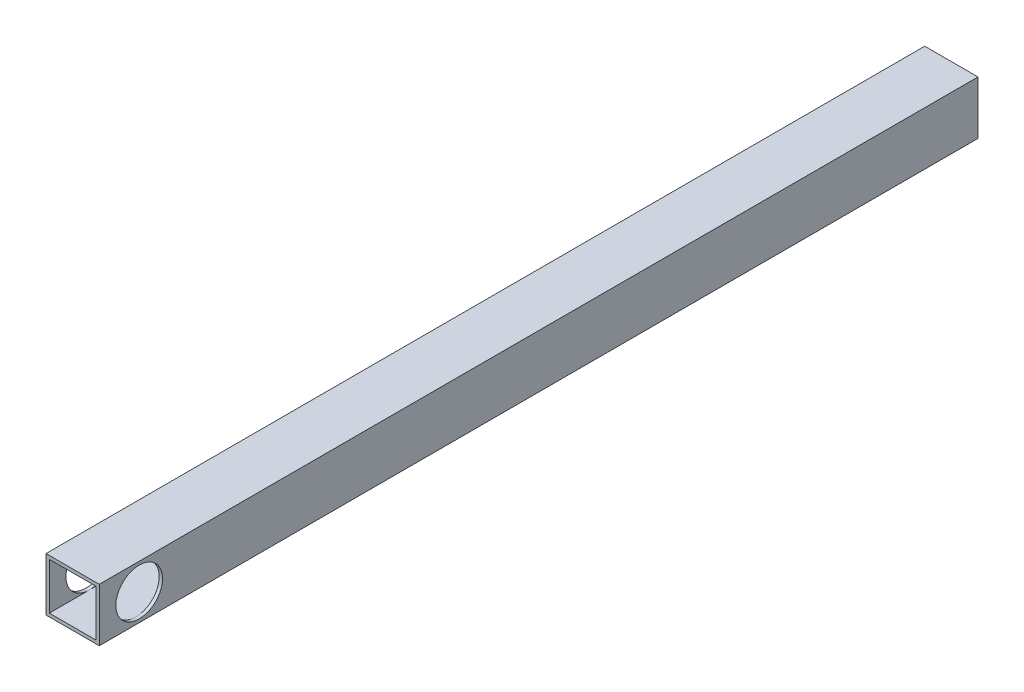
SolidWorks part; units mm, degrees
material "6061 Alloy"
ref_plane "Front Plane" through (0, 0, 0) normal (0, 0, 1) x (1, 0, 0)
ref_plane "Top Plane" through (0, 0, 0) normal (0, 1, 0) x (1, 0, 0)
ref_plane "Right Plane" through (0, 0, 0) normal (1, 0, 0) x (0, 0, -1)
sketch "Sketch1" plane through (0, 0, 0) normal (0, 0, 1) x (1, 0, 0)
  line L1 (12.7, -12.7) -> (-12.7, -12.7)
  line L2 (12.7, -12.7) -> (12.7, 12.7)
  line L3 (12.7, 12.7) -> (-12.7, 12.7)
  line L4 (-12.7, -12.7) -> (-12.7, 12.7)
  line L5 (12.7, -12.7) -> (-12.7, 12.7) construction
  line L6 (12.7, 12.7) -> (-12.7, -12.7) construction
  point P0 (0, 0)
  dimension "D1" = 25.4
extrude "Extrude-Thin1" add sketch "Sketch1" along normal blind 419.1 thin thin type one direction reverse wall 1.5875
sketch "Sketch2" plane through (12.7, 0, 0) normal (1, 0, 0) x (0, 0, -1)
  line L0 (-419.1, -12.7) -> (-419.1, 12.7) construction
  line L1 (-419.1, -12.7) -> (0, -12.7) construction
  circle A0 centre (-400.05, 0) radius 11.1125
  dimension "D1" = 22.225
  dimension "D2" = 19.05
  dimension "D3" = 12.7
extrude "Cut-Extrude1" cut sketch "Sketch2" against normal through all
